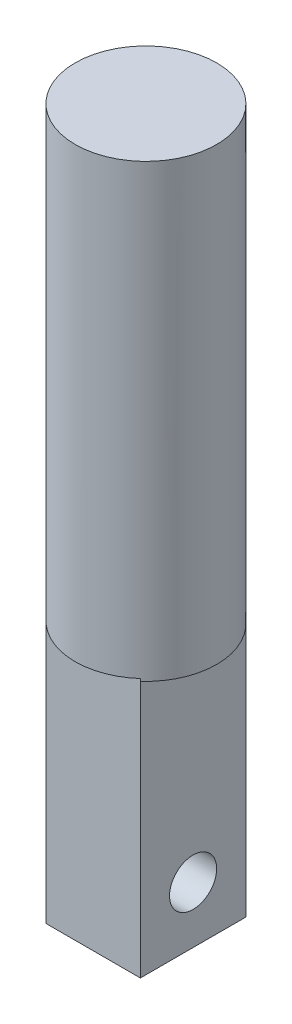
SolidWorks part; units mm, degrees
ref_plane "Front Plane" through (0, 0, 0) normal (0, 0, 1) x (1, 0, 0)
ref_plane "Top Plane" through (0, 0, 0) normal (0, 1, 0) x (1, 0, 0)
ref_plane "Right Plane" through (0, 0, 0) normal (1, 0, 0) x (0, 0, -1)
sketch "Sketch2" plane through (0, 0, 0) normal (0, 1, 0) x (1, 0, 0)
  circle A0 centre (0, 0) radius 15
  dimension "D1" = 30
extrude "Boss-Extrude1" add sketch "Sketch2" along normal blind 150
sketch "Sketch3" plane through (0, 0, 0) normal (1, 0, 0) x (0, 0, -1)
  line L0 (15, 0) -> (15, 150) construction
  line L1 (-15, -54.4944) -> (15, -54.4944)
  line L2 (-15, -54.4944) -> (-15, 54.4944)
  line L3 (-15, 54.4944) -> (15, 54.4944)
  line L4 (15, -54.4944) -> (15, 54.4944)
  line L5 (-15, -54.4944) -> (15, 54.4944) construction
  line L6 (-15, 54.4944) -> (15, -54.4944) construction
  point P0 (0, 0)
extrude "Cut-Extrude1" cut sketch "Sketch3" along normal blind 100 from offset 10
extrude "Cut-Extrude2" cut sketch "Sketch3<2>" against normal blind 100 from offset 10 offset against normal yes
sketch "Sketch3<2>" plane through (0, 0, 0) normal (1, 0, 0) x (0, 0, -1) same geometry as "Sketch3"
sketch "Sketch4" plane through (10, 0, 0) normal (1, 0, 0) x (0, 0, -1)
  line L0 (11.1803, 54.4944) -> (11.1803, 0) construction
  line L1 (11.1803, 0) -> (-11.1803, 0) construction
  circle A0 centre (0.0003, 12) radius 5
  dimension "D1" = 10
  dimension "D2" = 11.18
  dimension "D3" = 12
extrude "Cut-Extrude3" cut sketch "Sketch4" against normal blind 100
sketch "Sketch5" plane through (0, 0, 0) normal (0, -1, 0) x (1, 0, 0)
  line L1 (-10, 11.1803) -> (10, 11.1803)
  line L3 (-10, -11.1803) -> (10, -11.1803)
  arc A0 (-10, -11.1803) -> (10, -11.1803) centre (0, 0) ccw
  arc A1 (10, 11.1803) -> (-10, 11.1803) centre (0, 0) ccw
  point P0 (0, 0)
  point P8 (-10, -11.1803)
  point P9 (0, 0)
  point P10 (-9.8595, 11.1803)
  point P13 (0, 0)
  point P14 (0, 0)
  point P15 (0, 0)
  point P16 (0, 0)
  point P17 (-10, 11.1803)
extrude "Cut-Extrude4" cut sketch "Sketch5" against normal blind 55
